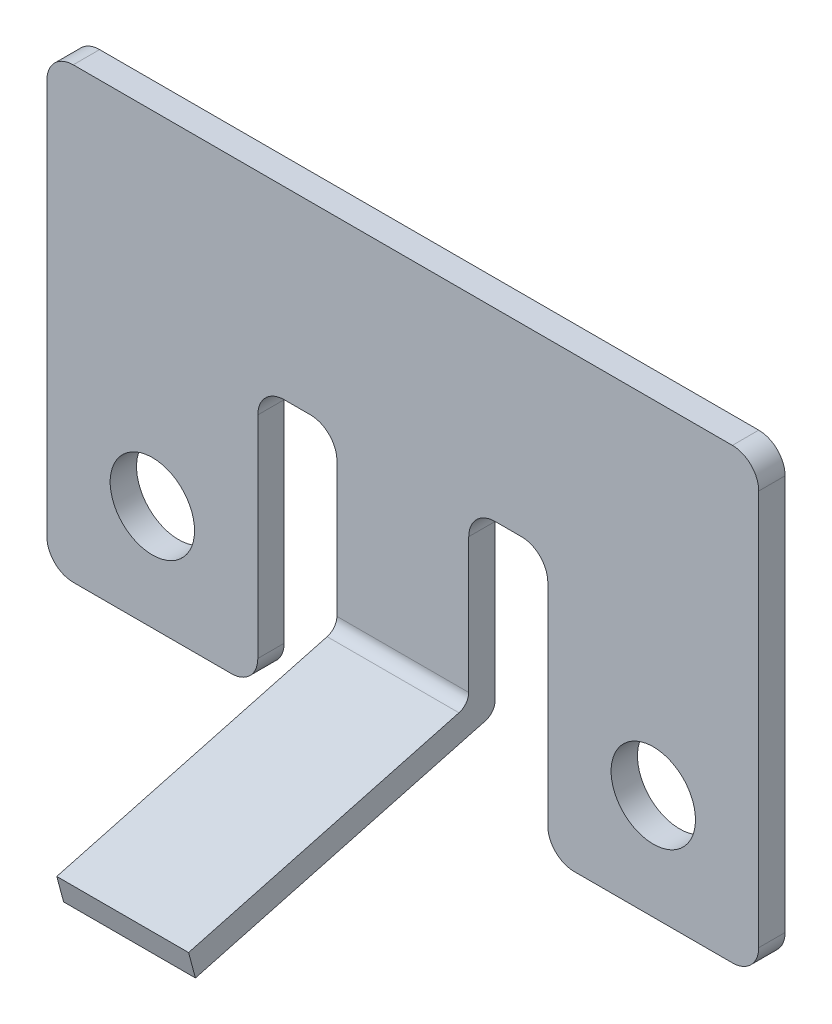
SolidWorks part; units mm, degrees
material "PET"
ref_plane "前视基准面" through (0, 0, 0) normal (0, 0, 1) x (1, 0, 0)
ref_plane "上视基准面" through (0, 0, 0) normal (0, 1, 0) x (1, 0, 0)
ref_plane "右视基准面" through (0, 0, 0) normal (1, 0, 0) x (0, 0, -1)
sketch "草图1" plane through (0, 0, 0) normal (0, 0, 1) x (1, 0, 0)
  line L0 (-9.5, 0) -> (9.5, 0) construction
  line L1 (-13.5, 12) -> (-13.5, -3)
  line L2 (-12.5, -4) -> (-6.5, -4)
  line L3 (-5.5, -3) -> (-5.5, 5)
  line L4 (-4.5, 6) -> (-3.5, 6)
  line L5 (-2.5, 5) -> (-2.5, -0.5)
  line L6 (-2.5, -0.5) -> (2.5, -0.5)
  line L7 (0, -0.5) -> (0, 0) construction
  line L8 (-12.5, 13) -> (12.5, 13)
  line L9 (12.5, -4) -> (6.5, -4)
  line L10 (2.5, 5) -> (2.5, -0.5)
  line L11 (4.5, 6) -> (3.5, 6)
  line L12 (5.5, -3) -> (5.5, 5)
  line L13 (13.5, 12) -> (13.5, -3)
  circle A0 centre (-9.5, 0) radius 1.6
  circle A1 centre (9.5, 0) radius 1.6
  arc A2 (13.5, 12) -> (12.5, 13) centre (12.5, 12) ccw
  arc A3 (-13.5, 12) -> (-12.5, 13) centre (-12.5, 12) cw
  arc A4 (6.5, -4) -> (5.5, -3) centre (6.5, -3) cw
  arc A5 (12.5, -4) -> (13.5, -3) centre (12.5, -3) ccw
  arc A6 (-6.5, -4) -> (-5.5, -3) centre (-6.5, -3) ccw
  arc A7 (-13.5, -3) -> (-12.5, -4) centre (-12.5, -3) ccw
  arc A8 (4.5, 6) -> (5.5, 5) centre (4.5, 5) cw
  arc A9 (2.5, 5) -> (3.5, 6) centre (3.5, 5) cw
  arc A10 (-5.5, 5) -> (-4.5, 6) centre (-4.5, 5) cw
  arc A11 (-3.5, 6) -> (-2.5, 5) centre (-3.5, 5) cw
  point P18 (0, 13)
  point P23 (13.5, 13)
  point P26 (-13.5, 13)
  point P29 (5.5, -4)
  point P32 (13.5, -4)
  point P35 (-5.5, -4)
  point P38 (-13.5, -4)
  point P41 (5.5, 6)
  point P44 (2.5, 6)
  point P47 (-5.5, 6)
  point P50 (-2.5, 6)
  dimension "D2" = 3.2
  dimension "D6" = 4
  dimension "D7" = 4
  dimension "D10" = 1
  dimension "D11" = 1
  dimension "D1" = 19
  dimension "D3" = 0.5
  dimension "D4" = 5
  dimension "D5" = 4
  dimension "D8" = 6
  dimension "D9" = 7
extrude "凸台-拉伸1" add sketch "草图1" along normal blind 1
sketch "草图2" plane through (2.5, 0, 0) normal (1, 0, 0) x (0, 0, -1)
  line L0 (-1, -0.5) -> (-11.6252, -3.347)
  line L1 (-11.6252, -3.347) -> (-11.3664, -4.3129)
  line L2 (-11.3664, -4.3129) -> (-0.3706, -1.3666)
  line L3 (0, -3) -> (0, 5) construction
  line L4 (0, -0.8837) -> (0, -0.5)
  line L5 (0, -0.5) -> (-1, -0.5)
  line L6 (-1, -0.5) -> (-1, 5) construction
  arc A0 (-0.3706, -1.3666) -> (0, -0.8837) centre (-0.5, -0.8837) ccw
  point P13 (0, -1.2673)
  dimension "D4" = 0.5
  dimension "D1" = 1
  dimension "D2" = 105
  dimension "D3" = 11
extrude "凸台-拉伸2" add sketch "草图2" against normal up to surface (5 mm away) up to face at (-2.5, 2.25, 0.5)
fillet "圆角1" radius 0.5 1 edges at (0, -0.5, 1)
